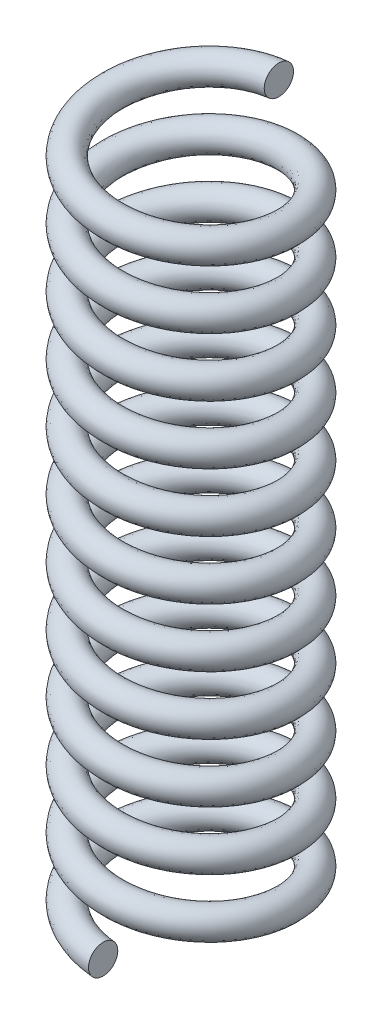
SolidWorks part; units mm, degrees
note: '?' marks a value the reader was unsure of.
ref_plane "前视基准面" through (0, 0, 0) normal (0, 0, 1) x (1, 0, 0)
ref_plane "上视基准面" through (0, 0, 0) normal (0, 1, 0) x (1, 0, 0)
ref_plane "右视基准面" through (0, 0, 0) normal (1, 0, 0) x (0, 0, -1)
ref_axis "基准轴1" through (0, 66, 0) along (0, -1, 0)?
sketch "草图4" plane through (0, 0, 0) normal (0, 1, 0) x (1, 0, 0)
  circle A0 centre (0, 0) radius 3
  dimension "D1" = 6
curve "螺旋线/涡状线1" pitch 2 height 23 turns 11.5
sketch "草图7" plane through (0, 0, 0) normal (1, 0, 0) x (0, 0, -1)
  circle A0 centre (-3, 0) radius 0.5
  spline S0 degree 3 poles (-3, 0) (-3, 0.0414) (-2.8438, 0.1251) (-2.1765, 0.25) (-1.1779, 0.375) (0, 0.5) (1.1779, 0.625) (2.1765, 0.75) (2.8438, 0.875) (3.0781, 1) (2.8438, 1.125) (2.1765, 1.25) (1.1779, 1.375) (0, 1.5) (-1.1779, 1.625) (-2.1765, 1.75) (-2.8438, 1.875) (-3.0781, 2) (-2.8438, 2.125) (-2.1765, 2.25) (-1.1779, 2.375) (0, 2.5) (1.1779, 2.625) (2.1765, 2.75) (2.8438, 2.875) (3.0781, 3) (2.8438, 3.125) (2.1765, 3.25) (1.1779, 3.375) (0, 3.5) (-1.1779, 3.625) (-2.1765, 3.75) (-2.8438, 3.875) (-3.0781, 4) (-2.8438, 4.125) (-2.1765, 4.25) (-1.1779, 4.375) (0, 4.5) (1.1779, 4.625) (2.1765, 4.75) (2.8438, 4.875) (3.0781, 5) (2.8438, 5.125) (2.1765, 5.25) (1.1779, 5.375) (0, 5.5) (-1.1779, 5.625) (-2.1765, 5.75) (-2.8438, 5.875) (-3.0781, 6) (-2.8438, 6.125) (-2.1765, 6.25) (-1.1779, 6.375) (0, 6.5) (1.1779, 6.625) (2.1765, 6.75) (2.8438, 6.875) (3.0781, 7) (2.8438, 7.125) (2.1765, 7.25) (1.1779, 7.375) (0, 7.5) (-1.1779, 7.625) (-2.1765, 7.75) (-2.8438, 7.875) (-3.0781, 8) (-2.8438, 8.125) (-2.1765, 8.25) (-1.1779, 8.375) (0, 8.5) (1.1779, 8.625) (2.1765, 8.75) (2.8438, 8.875) (3.0781, 9) (2.8438, 9.125) (2.1765, 9.25) (1.1779, 9.375) (0, 9.5) (-1.1779, 9.625) (-2.1765, 9.75) (-2.8438, 9.875) (-3.0781, 10) (-2.8438, 10.125) (-2.1765, 10.25) (-1.1779, 10.375) (0, 10.5) (1.1779, 10.625) (2.1765, 10.75) (2.8438, 10.875) (3.0781, 11) (2.8438, 11.125) (2.1765, 11.25) (1.1779, 11.375) (0, 11.5) (-1.1779, 11.625) (-2.1765, 11.75) (-2.8438, 11.875) (-3.0781, 12) (-2.8438, 12.125) (-2.1765, 12.25) (-1.1779, 12.375) (0, 12.5) (1.1779, 12.625) (2.1765, 12.75) (2.8438, 12.875) (3.0781, 13) (2.8438, 13.125) (2.1765, 13.25) (1.1779, 13.375) (0, 13.5) (-1.1779, 13.625) (-2.1765, 13.75) (-2.8438, 13.875) (-3.0781, 14) (-2.8438, 14.125) (-2.1765, 14.25) (-1.1779, 14.375) (0, 14.5) (1.1779, 14.625) (2.1765, 14.75) (2.8438, 14.875) (3.0781, 15) (2.8438, 15.125) (2.1765, 15.25) (1.1779, 15.375) (0, 15.5) (-1.1779, 15.625) (-2.1765, 15.75) (-2.8438, 15.875) (-3.0781, 16) (-2.8438, 16.125) (-2.1765, 16.25) (-1.1779, 16.375) (0, 16.5) (1.1779, 16.625) (2.1765, 16.75) (2.8438, 16.875) (3.0781, 17) (2.8438, 17.125) (2.1765, 17.25) (1.1779, 17.375) (0, 17.5) (-1.1779, 17.625) (-2.1765, 17.75) (-2.8438, 17.875) (-3.0781, 18) (-2.8438, 18.125) (-2.1765, 18.25) (-1.1779, 18.375) (0, 18.5) (1.1779, 18.625) (2.1765, 18.75) (2.8438, 18.875) (3.0781, 19) (2.8438, 19.125) (2.1765, 19.25) (1.1779, 19.375) (0, 19.5) (-1.1779, 19.625) (-2.1765, 19.75) (-2.8438, 19.875) (-3.0781, 20) (-2.8438, 20.125) (-2.1765, 20.25) (-1.1779, 20.375) (0, 20.5) (1.1779, 20.625) (2.1765, 20.75) (2.8438, 20.875) (3.0781, 21) (2.8438, 21.125) (2.1765, 21.25) (1.1779, 21.375) (0, 21.5) (-1.1779, 21.625) (-2.1765, 21.75) (-2.8438, 21.875) (-3.0781, 22) (-2.8438, 22.125) (-2.1765, 22.25) (-1.1779, 22.375) (0, 22.5) (1.1779, 22.625) (2.1765, 22.75) (2.8438, 22.8749) (3, 22.9586) (3, 23) knots 0 0 0 0 0.005435 0.01087 0.016304 0.021739 0.027174 0.032609 0.038043 0.043478 0.048913 0.054348 0.059783 0.065217 0.070652 0.076087 0.081522 0.086957 0.092391 0.097826 0.103261 0.108696 0.11413 0.119565 0.125 0.130435 0.13587 0.141304 0.146739 0.152174 0.157609 0.163043 0.168478 0.173913 0.179348 0.184783 0.190217 0.195652 0.201087 0.206522 0.211957 0.217391 0.222826 0.228261 0.233696 0.23913 0.244565 0.25 0.255435 0.26087 0.266304 0.271739 0.277174 0.282609 0.288043 0.293478 0.298913 0.304348 0.309783 0.315217 0.320652 0.326087 0.331522 0.336957 0.342391 0.347826 0.353261 0.358696 0.36413 0.369565 0.375 0.380435 0.38587 0.391304 0.396739 0.402174 0.407609 0.413043 0.418478 0.423913 0.429348 0.434783 0.440217 0.445652 0.451087 0.456522 0.461957 0.467391 0.472826 0.478261 0.483696 0.48913 0.494565 0.5 0.505435 0.51087 0.516304 0.521739 0.527174 0.532609 0.538043 0.543478 0.548913 0.554348 0.559783 0.565217 0.570652 0.576087 0.581522 0.586957 0.592391 0.597826 0.603261 0.608696 0.61413 0.619565 0.625 0.630435 0.63587 0.641304 0.646739 0.652174 0.657609 0.663043 0.668478 0.673913 0.679348 0.684783 0.690217 0.695652 0.701087 0.706522 0.711957 0.717391 0.722826 0.728261 0.733696 0.73913 0.744565 0.75 0.755435 0.76087 0.766304 0.771739 0.777174 0.782609 0.788043 0.793478 0.798913 0.804348 0.809783 0.815217 0.820652 0.826087 0.831522 0.836957 0.842391 0.847826 0.853261 0.858696 0.86413 0.869565 0.875 0.880435 0.88587 0.891304 0.896739 0.902174 0.907609 0.913043 0.918478 0.923913 0.929348 0.934783 0.940217 0.945652 0.951087 0.956522 0.961957 0.967391 0.972826 0.978261 0.983696 0.98913 0.994565 1 1 1 1 construction
  point P4 (0, 0)
  dimension "D1" = 1
sweep "扫描1" add profiles "草图7" path "螺旋线/涡状线1"
